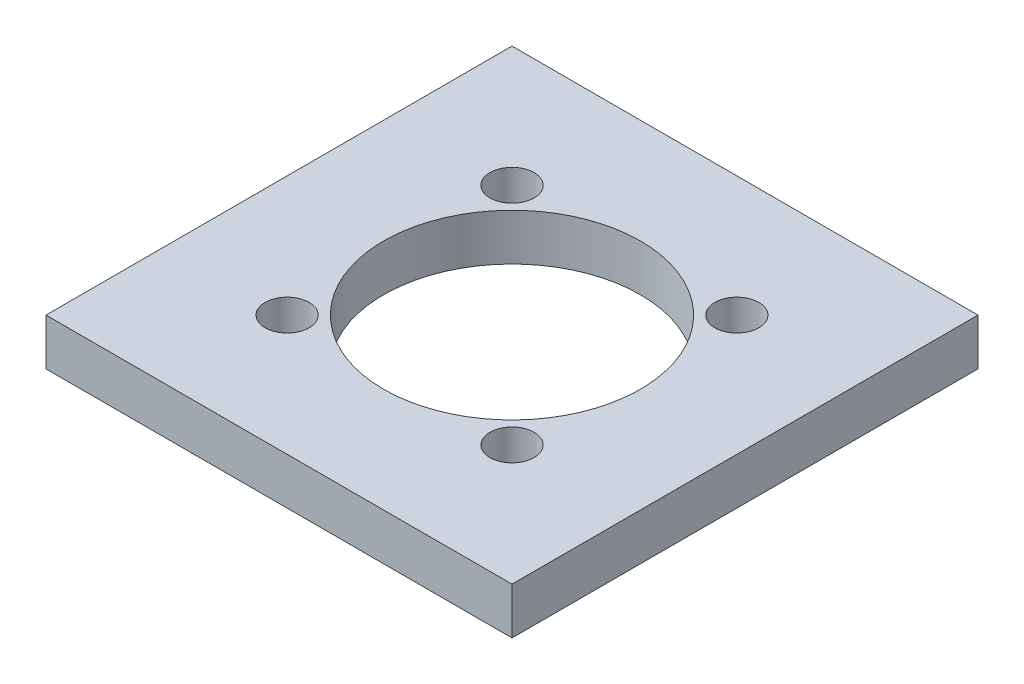
SolidWorks part; units mm, degrees
ref_plane "Front Plane" through (0, 0, 0) normal (0, 0, 1) x (1, 0, 0)
ref_plane "Top Plane" through (0, 0, 0) normal (0, 1, 0) x (1, 0, 0)
ref_plane "Right Plane" through (0, 0, 0) normal (1, 0, 0) x (0, 0, -1)
sketch "Sketch2" plane through (0, 0, 0) normal (0, 1, 0) x (1, 0, 0)
  line L1 (-19.05, -19.05) -> (19.05, -19.05)
  line L2 (-19.05, -19.05) -> (-19.05, 19.05)
  line L3 (-19.05, 19.05) -> (19.05, 19.05)
  line L4 (19.05, -19.05) -> (19.05, 19.05)
  line L5 (-19.05, -19.05) -> (19.05, 19.05) construction
  line L6 (-19.05, 19.05) -> (19.05, -19.05) construction
  point P0 (0, 0)
  dimension "D2" = 38.1
extrude "Boss-Extrude1" add sketch "Sketch2" along normal blind 3.81
sketch "Sketch4" plane through (0, 3.81, 0) normal (0, 1, 0) x (1, 0, 0)
  line L0 (-9.1924, 9.1924) -> (9.1924, -9.1924) construction
  line L1 (-10.5, 0) -> (10.5, 0) construction
  line L2 (9.1924, 9.1924) -> (-9.1924, -9.1924) construction
  circle A0 centre (0, 0) radius 10.5
  point P9 (0, 0)
  point P10 (9.1924, 9.1924)
  point P11 (-9.1924, -9.1924)
  dimension "D3" = 21
  dimension "D1" = 26
  dimension "D2" = 45
  dimension "D4" = 45
extrude "Cut-Extrude1" cut sketch "Sketch4" against normal through all
hole_wizard "M3 Clearance Hole2" positions "3DSketch5" profile "Sketch9" hole size "M3" standard "ANSI Metric" end condition through all
sketch3d "3DSketch5"
  point P0 (-9.1924, 3.81, -9.1924)
  point P3 (9.1924, 3.81, 9.1924)
  point P6 (9.1924, 3.81, -9.1924)
  point P9 (-9.1924, 3.81, 9.1924)
sketch "Sketch9" plane through (-9.1924, 3.81, -9.1924) normal (1, 0, 0) x (0, 0, 1)
  line L0 (0, 0) -> (0, 3.81)
  line L1 (0, 3.81) -> (1.8, 3.81)
  line L2 (1.8, 3.81) -> (1.8, 0)
  line L5 (1.8, 0) -> (0, 0)
  line L11 (0, -6.35) -> (0, 107.95) construction
  dimension "Thru Hole Dia." = 3.6
  dimension "Thru Hole Depth" = 3.81
